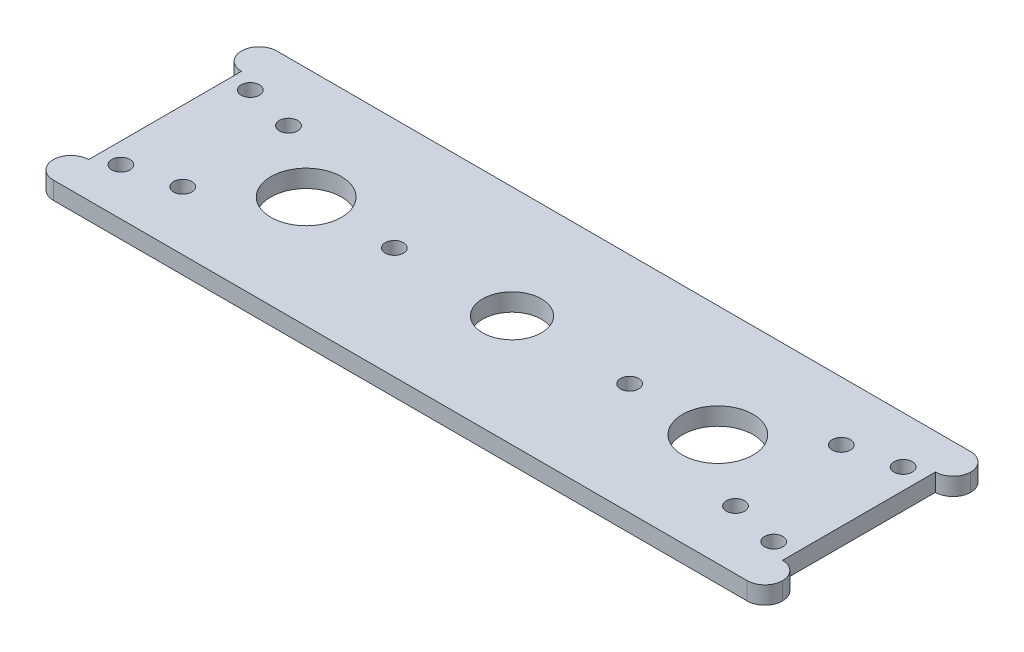
SolidWorks part; units mm, degrees
material "Thornel Mat VMA"
ref_plane "Front Plane" through (0, 0, 0) normal (0, 0, 1) x (1, 0, 0)
ref_plane "Top Plane" through (0, 0, 0) normal (0, 1, 0) x (1, 0, 0)
ref_plane "Right Plane" through (0, 0, 0) normal (1, 0, 0) x (0, 0, -1)
sketch "Sketch1" plane through (0, 0, 0) normal (0, 1, 0) x (1, 0, 0)
  line L0 (0, 0) -> (0, 56.5511) construction
  line L1 (0, 0) -> (118.6796, 0) construction
  line L2 (-62, 19) -> (62, 19)
  line L5 (-62, -19) -> (62, -19)
  line L6 (62, 19) -> (62, 13)
  line L7 (62, 13) -> (59, 13)
  line L8 (59, 13) -> (59, -13)
  line L9 (62, -13) -> (59, -13)
  line L10 (62, -19) -> (62, -13)
  line L11 (-62, -19) -> (-62, -13)
  line L12 (-62, -13) -> (-59, -13)
  line L13 (-59, 13) -> (-59, -13)
  line L14 (-62, 13) -> (-59, 13)
  line L15 (-62, 19) -> (-62, 13)
  circle A0 centre (55.5, 11) radius 1.55
  circle A1 centre (-55.5, 11) radius 1.55
  circle A2 centre (-55.5, -11) radius 1.55
  circle A3 centre (55.5, -11) radius 1.55
  circle A4 centre (0, 0) radius 5
  circle A5 centre (20, 0) radius 1.55
  circle A6 centre (-20, 0) radius 1.55
  circle A7 centre (35, 0) radius 6
  circle A8 centre (-35, 0) radius 6
  circle A9 centre (47, 9) radius 1.55
  circle A10 centre (47, -9) radius 1.55
  circle A11 centre (-47, -9) radius 1.55
  circle A12 centre (-47, 9) radius 1.55
  point P13 (0, 19)
  point P18 (-61, 0)
  point P19 (61, 0)
  point P28 (59, 0)
  dimension "D1" = 3.1
  dimension "D2" = 3.5
  dimension "D3" = 8
  dimension "D4" = 3.1
  dimension "D5" = 10
  dimension "D6" = 20
  dimension "D11" = 35
  dimension "D12" = 12
  dimension "D13" = 8.5
  dimension "D14" = 2
  dimension "D7" = 38
  dimension "D8" = 124
  dimension "D9" = 3
  dimension "D10" = 6
extrude "Boss-Extrude1" add sketch "Sketch1" along normal blind 3
fillet "Fillet1" radius 3 8 edges at (-62, 1.5, -19) (-62, 1.5, -13) (-62, 1.5, 13) (-62, 1.5, 19) (62, 1.5, 19) (62, 1.5, 13) (62, 1.5, -13) (62, 1.5, -19)
